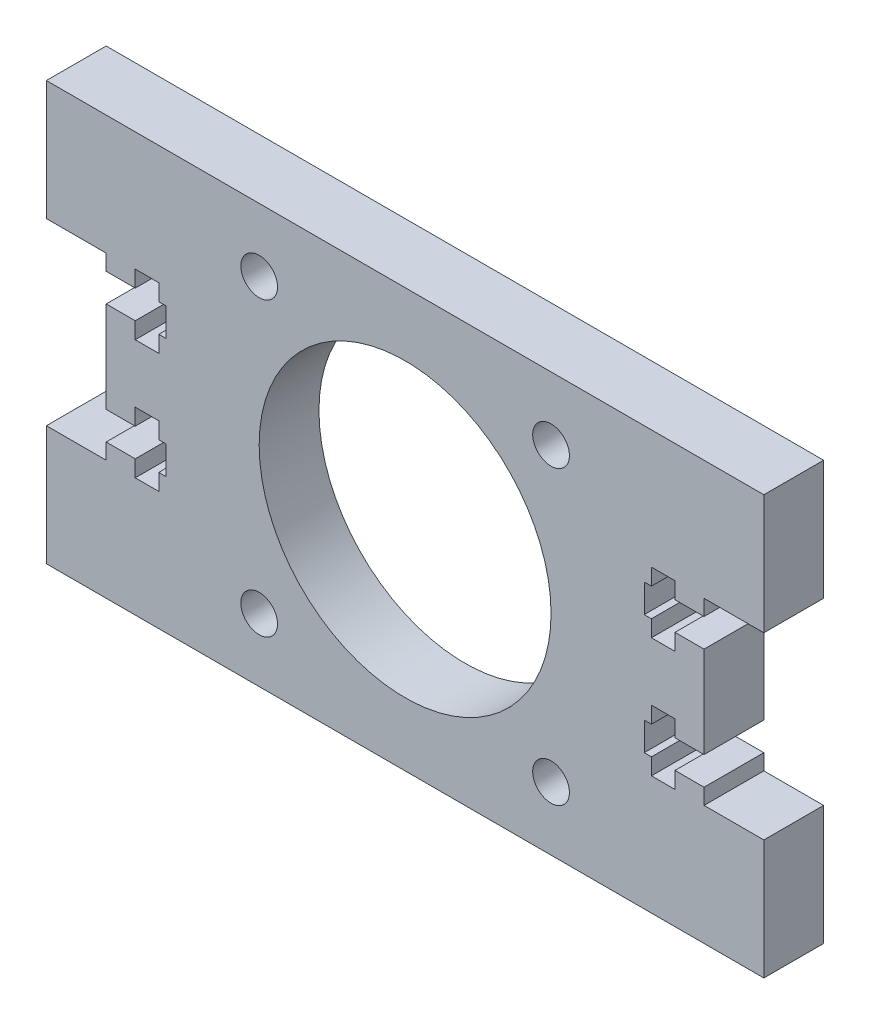
SolidWorks part; units mm, degrees
ref_plane "Front Plane" through (0, 0, 0) normal (0, 0, 1) x (1, 0, 0)
ref_plane "Top Plane" through (0, 0, 0) normal (0, 1, 0) x (1, 0, 0)
ref_plane "Right Plane" through (0, 0, 0) normal (1, 0, 0) x (0, 0, -1)
sketch "Sketch2" plane through (0, 0, 0) normal (0, 0, 1) x (1, 0, 0)
  line L0 (0, 22.225) -> (63.5, 22.225) construction
  line L1 (0, 0) -> (63.5, 0)
  line L2 (0, 12.7) -> (0, 14.375)
  line L3 (0, 44.45) -> (63.5, 44.45)
  line L4 (63.5, 0) -> (63.5, 44.45)
  line L5 (31.75, 44.45) -> (31.75, 0) construction
  line L6 (5.588, 30.075) -> (5.588, 31.825)
  line L7 (0, 0) -> (-3.175, 0)
  line L8 (0, 17.375) -> (0, 31.75)
  line L9 (0, 12.7) -> (-3.175, 12.7)
  line L10 (-3.175, 0) -> (-3.175, 12.7)
  line L11 (0, 17.375) -> (3.088, 17.375)
  line L12 (3.088, 14.375) -> (3.088, 12.625)
  line L13 (0, 14.375) -> (3.088, 14.375)
  line L14 (6.35, 17.375) -> (6.35, 14.375)
  line L15 (60.412, 14.375) -> (60.412, 12.625)
  line L16 (3.088, 19.125) -> (5.588, 19.125)
  line L17 (3.088, 19.125) -> (3.088, 17.375)
  line L18 (3.088, 12.625) -> (5.588, 12.625)
  line L19 (5.588, 19.125) -> (5.588, 17.375)
  line L20 (57.912, 27.075) -> (57.15, 27.075)
  line L21 (5.588, 14.375) -> (5.588, 12.625)
  line L22 (57.912, 30.075) -> (57.912, 31.825)
  line L23 (57.912, 30.075) -> (57.15, 30.075)
  line L24 (5.588, 25.325) -> (5.588, 27.075)
  line L25 (3.088, 31.825) -> (5.588, 31.825)
  line L26 (3.088, 25.325) -> (3.088, 27.075)
  line L27 (3.088, 25.325) -> (5.588, 25.325)
  line L28 (6.35, 27.075) -> (6.35, 30.075)
  line L29 (0, 30.075) -> (3.088, 30.075)
  line L30 (5.588, 17.375) -> (6.35, 17.375)
  line L31 (0, 27.075) -> (3.088, 27.075)
  line L32 (-3.175, 44.45) -> (-3.175, 31.75)
  line L33 (0, 31.75) -> (-3.175, 31.75)
  line L34 (5.588, 30.075) -> (6.35, 30.075)
  line L35 (0, 44.45) -> (-3.175, 44.45)
  line L42 (63.5, 44.45) -> (66.675, 44.45)
  line L43 (5.588, 14.375) -> (6.35, 14.375)
  line L44 (63.5, 31.75) -> (66.675, 31.75)
  line L45 (66.675, 44.45) -> (66.675, 31.75)
  line L46 (63.5, 27.075) -> (60.412, 27.075)
  line L47 (57.912, 14.375) -> (57.15, 14.375)
  line L48 (63.5, 30.075) -> (60.412, 30.075)
  line L49 (57.15, 27.075) -> (57.15, 30.075)
  line L50 (60.412, 25.325) -> (57.912, 25.325)
  line L51 (60.412, 25.325) -> (60.412, 27.075)
  line L52 (60.412, 31.825) -> (57.912, 31.825)
  line L53 (57.912, 25.325) -> (57.912, 27.075)
  line L54 (57.912, 19.125) -> (57.912, 17.375)
  line L55 (60.412, 12.625) -> (57.912, 12.625)
  line L56 (60.412, 19.125) -> (60.412, 17.375)
  line L57 (60.412, 19.125) -> (57.912, 19.125)
  line L58 (57.15, 17.375) -> (57.15, 14.375)
  line L59 (63.5, 14.375) -> (60.412, 14.375)
  line L60 (5.588, 27.075) -> (6.35, 27.075)
  line L61 (63.5, 17.375) -> (60.412, 17.375)
  line L62 (66.675, 0) -> (66.675, 12.7)
  line L63 (63.5, 12.7) -> (66.675, 12.7)
  line L64 (3.088, 30.075) -> (3.088, 31.825)
  line L65 (63.5, 0) -> (66.675, 0)
  line L66 (57.912, 14.375) -> (57.912, 12.625)
  line L67 (57.912, 17.375) -> (57.15, 17.375)
  line L70 (60.412, 30.075) -> (60.412, 31.825)
  circle A0 centre (16.25, 37.725) radius 1.95
  circle A1 centre (47.25, 37.725) radius 1.95
  circle A2 centre (47.25, 6.725) radius 1.95
  circle A3 centre (16.25, 6.725) radius 1.95
  circle A4 centre (31.75, 22.225) radius 15.5
  point P28 (4.338, 15.875)
  point P46 (4.338, 28.575)
  point P73 (59.162, 28.575)
  point P74 (59.162, 15.875)
  dimension "D3" = 3.9
  dimension "D6" = 31
  dimension "D1" = 44.45
  dimension "D2" = 63.5
  dimension "D4" = 31
  dimension "D5" = 31
  dimension "D7" = 3.175
  dimension "D8" = 12.7
  dimension "D9" = 0.762
  dimension "D10" = 2.5
  dimension "D11" = 6.35
  dimension "D12" = 3
  dimension "D13" = 6.5
extrude "Boss-Extrude1" add sketch "Sketch2" along normal blind 6.35 contours L70 L48 L4 L3 L35 L32 L33 L8 L29 L64 L25 L6 L34 L28 L60 L24 L27 L26 L31 L11 L17 L16 L19 L30 L14 L43 L21 L18 L12 L13 L2 L9 L10 L7 L1 L59 L15 L55 L66 L47 L58 L67 L54 L57 L56 L61 | L4 L65 L62 L63 | L45 L42 L4 L44 region at (-1.5875, 0.8013, 0) region at (65.0875, 6.35, 0) region at (65.0875, 38.1, 0)
sketch "Sketch3" plane through (0, 0, 0) normal (0, 0, -1) x (-1, 0, 0)
  line L0 (-31.75, 0) -> (-31.75, 44.45) construction
  line L1 (-66.675, 0) -> (3.175, 0) construction
  line L2 (3.175, 44.45) -> (-66.675, 44.45) construction
  line L3 (0, 12.7) -> (3.175, 12.7) construction
  line L4 (3.175, 0) -> (6.35, 0)
  line L5 (3.175, 0) -> (3.175, 12.7)
  line L6 (3.175, 12.7) -> (6.35, 12.7)
  line L7 (6.35, 0) -> (6.35, 12.7)
  line L8 (0, 31.75) -> (3.175, 31.75) construction
  line L9 (3.175, 44.45) -> (6.35, 44.45)
  line L10 (3.175, 44.45) -> (3.175, 31.75)
  line L11 (3.175, 31.75) -> (6.35, 31.75)
  line L12 (6.35, 44.45) -> (6.35, 31.75)
  line L13 (-69.85, 44.45) -> (-69.85, 31.75)
  line L14 (-66.675, 31.75) -> (-69.85, 31.75)
  line L15 (-66.675, 44.45) -> (-66.675, 31.75)
  line L16 (-66.675, 44.45) -> (-69.85, 44.45)
  line L17 (-69.85, 0) -> (-69.85, 12.7)
  line L18 (-66.675, 12.7) -> (-69.85, 12.7)
  line L19 (-66.675, 0) -> (-66.675, 12.7)
  line L20 (-66.675, 0) -> (-69.85, 0)
  dimension "D1" = 3.175
  dimension "D2" = 3.175
extrude "Boss-Extrude2" add sketch "Sketch3" against normal blind 6.35
